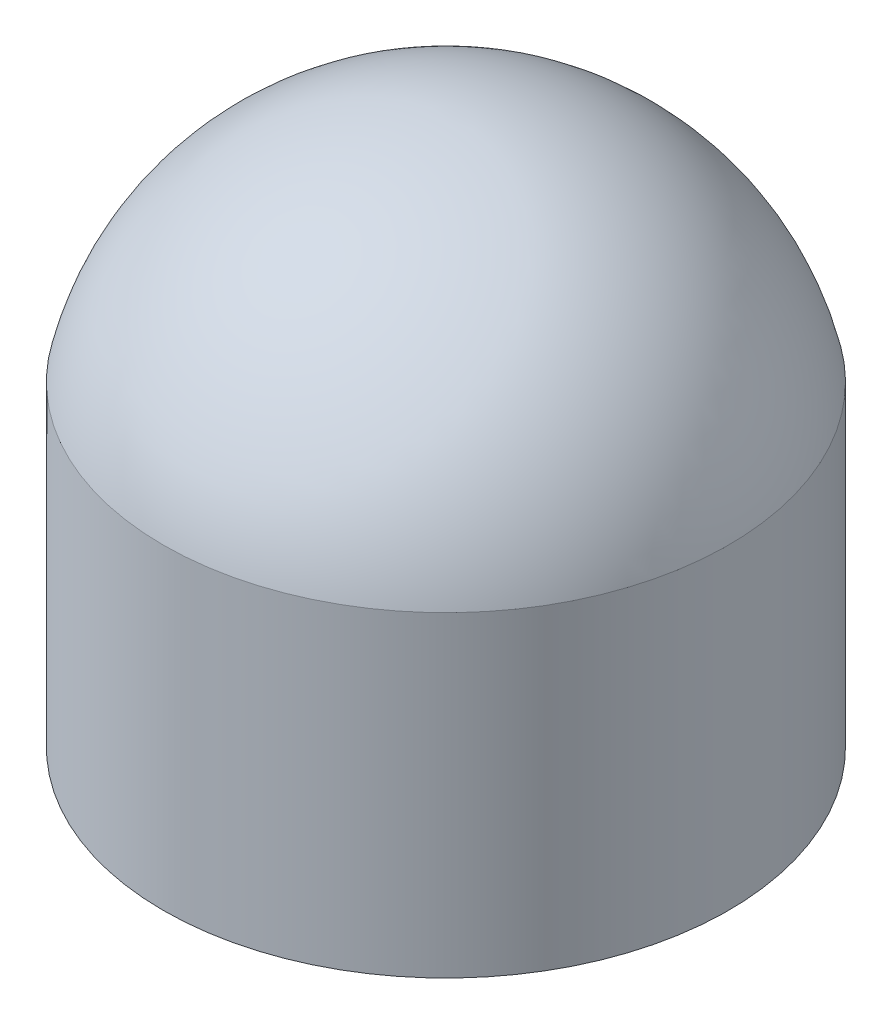
SolidWorks part; units mm, degrees
material "1023 Carbon Steel Sheet (SS)"
ref_plane "Front Plane" through (0, 0, 0) normal (0, 0, 1) x (1, 0, 0)
ref_plane "Top Plane" through (0, 0, 0) normal (0, 1, 0) x (1, 0, 0)
ref_plane "Right Plane" through (0, 0, 0) normal (1, 0, 0) x (0, 0, -1)
sketch "Sketch1" plane through (0, 0, 0) normal (0, 1, 0) x (1, 0, 0)
  line L0 (0, 1.25) -> (0, -1.25) construction
  circle A0 centre (0, 0) radius 1.25
  dimension "D1" = 2.5
extrude "Boss-Extrude1" add sketch "Sketch1" along normal blind 1.4
dome "Dome1" faces to dome 1 distance 1 reverse direction no elliptical dome no face at (0, 1.4, 1.25) parameters "D1"=1
